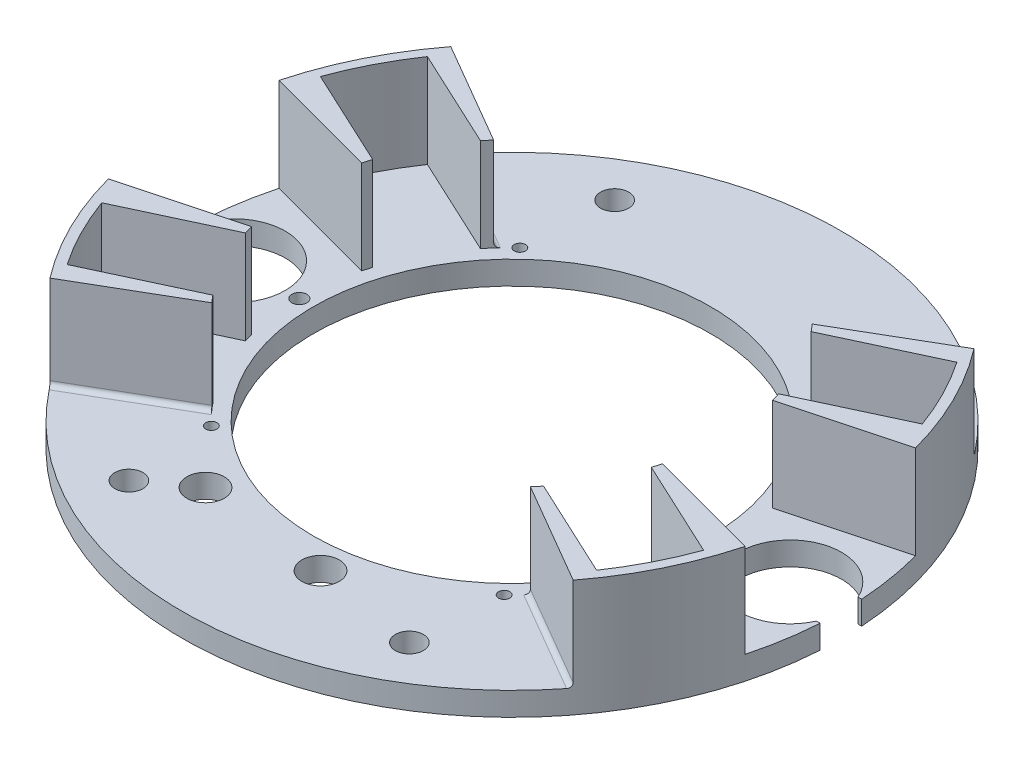
SolidWorks part; units mm, degrees
ref_plane "Front Plane" through (0, 0, 0) normal (0, 0, 1) x (1, 0, 0)
ref_plane "Top Plane" through (0, 0, 0) normal (0, 1, 0) x (1, 0, 0)
ref_plane "Right Plane" through (0, 0, 0) normal (1, 0, 0) x (0, 0, -1)
sketch "Sketch1" plane through (0, 0, 0) normal (0, 1, 0) x (1, 0, 0)
  circle A0 centre (0, 0) radius 53.975
  circle A1 centre (0, 0) radius 89.535
  dimension "D1" = 107.95
  dimension "D2" = 35.56
extrude "Base " add sketch "Sketch1" along normal blind 6.35
sketch "Sketch2" plane through (0, 6.35, 0) normal (0, 1, 0) x (1, 0, 0)
  line L0 (0, 0) -> (0, 53.975) construction
  line L1 (0, 0) -> (75.565, 0) construction
  line L2 (88.3404, 5.6524) -> (89.3564, 5.6524)
  line L3 (88.3404, -5.6524) -> (89.3564, -5.6524)
  circle A0 centre (0, 0) radius 53.975 construction
  circle A1 centre (0, 0) radius 89.535 construction
  circle A2 centre (0, 0) radius 89.535
  circle A3 centre (0, 0) radius 53.975
  arc A4 (88.3404, 5.6524) -> (88.3404, -5.6524) centre (75.565, 0) ccw
  dimension "D2" = 27.94
  dimension "D1" = 1.016
extrude "Noce Cone Pyros " cut sketch "Sketch2" against normal up to surface (6.35 mm away) contours A4 region at (75.6474, 6.35, 0) up to face at (0, 0, 89.535)
mirror "Nose Cone Pyro mirror " about plane through (0, 0, 0) normal (1, 0, 0) of "Noce Cone Pyros "
sketch "Sketch3" plane through (0, 6.35, 0) normal (0, 1, 0) x (1, 0, 0)
  line L0 (0, 0) -> (0, 53.975) construction
  line L1 (52.1358, 13.9698) -> (86.4842, 23.1734)
  line L2 (0, 0) -> (53.975, 0) construction
  line L3 (44.9222, 36.347) -> (74.256, 50.0256)
  line L4 (43.2815, 38.286) -> (71.074, 54.4518)
  line L5 (54.8014, 17.1318) -> (81.7661, 29.7057)
  circle A0 centre (0, 0) radius 53.975 construction
  circle A1 centre (0, 0) radius 89.535 construction
  circle A2 centre (0, 0) radius 89.535
  circle A3 centre (0, 0) radius 53.975
  circle A4 centre (0, 0) radius 86.995
  circle A5 centre (0, 0) radius 57.785
  arc A7 (-89.535, 0) -> (89.535, 0) centre (0, 0) ccw construction
  dimension "D1" = 15
  dimension "D2" = 90
  dimension "D3" = 21.59
  dimension "D5" = 5.185
  dimension "D7" = 10
  dimension "D8" = 2.54
  dimension "D4" = 2.54
  dimension "D6" = 3.81
extrude "Battery 1 Holder " add sketch "Sketch3" along normal blind 25.4 contours A4 L3 L4 | A5 L3 A4 L4 | A4 L1 L3 | L1 A4 L5 region at (71.5669, 6.35, -21.982) region at (79.9182, 6.35, -36.5031) region at (58.8023, 6.35, -44.9995) region at (71.5588, 6.35, -51.6651)
mirror "Batery 2 Holder " about plane through (0, 0, 0) normal (0, 0, 1) of "Battery 1 Holder "
mirror "Battery 3 Holder " about plane through (0, 0, 0) normal (1, 0, 0) of "Battery 1 Holder "
mirror "Battery 4 Holder " about plane through (0, 0, 0) normal (1, 0, 0) of "Batery 2 Holder "
sketch "Sketch4" plane through (0, 6.35, 0) normal (0, 1, 0) x (1, 0, 0)
  line L0 (0, 0) -> (0, -63.5) construction
  line L1 (0, 0) -> (38.1, 65.9911) construction
  circle A0 centre (0, 0) radius 53.975 construction
  circle A1 centre (38.1, 65.9911) radius 3.81
  dimension "D3" = 7.62
  dimension "D1" = 30
  dimension "D2" = 76.2
extrude "Bolt Hole " cut sketch "Sketch4" against normal up to surface (6.35 mm away) up to face at (0, 0, 53.975)
mirror "Bolt Hole 2 " about plane through (0, 0, 0) normal (0, 0, 1) of "Bolt Hole "
mirror "Bolt Hole 3 " about plane through (0, 0, 0) normal (1, 0, 0) of "Bolt Hole "
mirror "Bolt Hole 4 " about plane through (0, 0, 0) normal (1, 0, 0) of "Bolt Hole 2 "
sketch "Sketch11" plane through (0, 0, 0) normal (0, -1, 0) x (1, 0, 0)
  line L0 (0, 0) -> (9.1284, 61.146) construction
  line L1 (0, 0) -> (-26.0597, 57.2093) construction
  line L2 (0, 0) -> (-61.595, 0) construction
  circle A0 centre (9.1284, 61.146) radius 5.08
  circle A1 centre (-26.0597, 57.2093) radius 5.08
  arc A2 (-88.3404, -5.6524) -> (-88.3404, 5.6524) centre (-75.565, 0) ccw construction
  dimension "D4" = 10.16
  dimension "D5" = 10.16
  dimension "D1" = 62.865
  dimension "D2" = 61.8236
  dimension "D3" = 35.4076
  dimension "D6" = 65.51
extrude "Cut-Extrude2" cut sketch "Sketch11" against normal up to surface (6.35 mm away) up to face at (-38.1, 6.35, 62.1811)
sketch "Sketch13" plane through (0, 0, 0) normal (0, -1, 0) x (1, 0, 0)
  line L0 (0, 0) -> (0, 41.91) construction
  line L1 (0, 41.91) -> (39.7764, 41.91) construction
  line L2 (0, 41.91) -> (-39.7764, 41.91) construction
  circle A2 centre (39.7764, 41.91) radius 3.175
  circle A3 centre (-39.7764, 41.91) radius 3.175
  dimension "D4" = 6.35
  dimension "D5" = 6.35
  dimension "D1" = 79.5528
  dimension "D2" = 41.91
  dimension "D3" = 39.7764
extrude "Cut-Extrude3" cut sketch "Sketch13" against normal blind 3.175
sketch "Sketch14" plane through (0, 3.175, 0) normal (0, -1, 0) x (1, 0, 0)
  circle A0 centre (39.7764, 41.91) radius 1.524
  circle A1 centre (-39.7764, 41.91) radius 1.524
  dimension "D1" = 3.048
  dimension "D2" = 3.048
extrude "Cut-Extrude4" cut sketch "Sketch14" against normal up to surface (3.175 mm away) up to face at (9.1284, 6.35, 66.226)
mirror "Mirror1" about plane through (0, 0, 0) normal (0, 0, 1) of "Cut-Extrude3", "Cut-Extrude4"
sketch "Sketch15" plane through (0, 0, 0) normal (0, -1, 0) x (1, 0, 0)
  line L0 (0, 0) -> (57.785, 0) construction
  circle A0 centre (57.785, 0) radius 2.032
  circle A2 centre (0, 0) radius 53.975 construction
  dimension "D1" = 4.064
  dimension "D2" = 57.785
fillet "Fillet3" radius 1.27 4 edges at (57.1778, 6.35, 46.3689) (-57.1778, 6.35, 46.3689) (-57.1778, 6.35, -46.3689) (57.1778, 6.35, -46.3689)
extrude "Cut-Extrude5" cut sketch "Sketch15" against normal up to surface (6.35 mm away) up to face at (39.7764, 6.35, -40.386)
mirror "Mirror2" about plane through (0, 0, 0) normal (1, 0, 0) of "Cut-Extrude5"
equation "\"0..800in\"=0.1"
